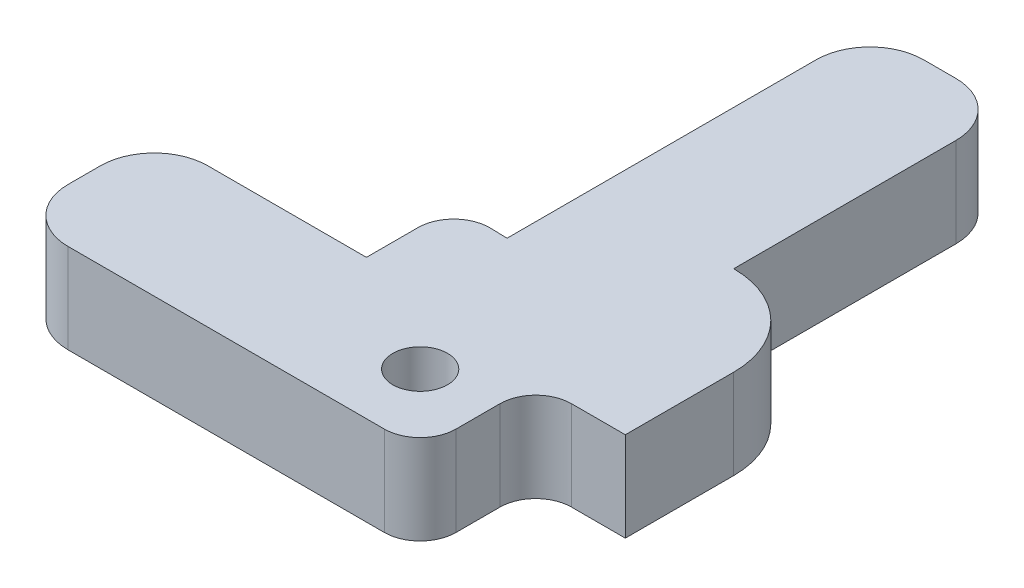
SolidWorks part; units mm, degrees
ref_plane "前视基准面" through (0, 0, 0) normal (0, 0, 1) x (1, 0, 0)
ref_plane "上视基准面" through (0, 0, 0) normal (0, 1, 0) x (1, 0, 0)
ref_plane "右视基准面" through (0, 0, 0) normal (1, 0, 0) x (0, 0, -1)
sketch "草图1" plane through (0, 0, 0) normal (0, 1, 0) x (1, 0, 0)
  line L0 (0, 0) -> (-3.75, 0) construction
  line L1 (8.75, 3.75) -> (8.75, 13.7657) construction
  line L2 (5.7467, -3.7343) -> (3.9, -3.7322) construction
  line L3 (-3.75, 8.75) -> (-3.75, 22) construction
  line L4 (-18.75, -0.75) -> (-18.75, 0.75) construction
  line L5 (5.7467, -3.7343) -> (5.7467, -6.2932) construction
  line L6 (0, 0) -> (3.75, 0) construction
  line L7 (3.75, 0) -> (8.75, 0) construction
  line L8 (8.75, 3.75) -> (8.75, -0.7343) construction
  line L9 (0.75, 29) -> (-0.75, 29) construction
  line L10 (-3.75, 0) -> (-8.75, 0) construction
  line L11 (5.7467, -3.7343) -> (5.7467, 16.2657) construction
  line L12 (-6.75, 3.75) -> (-10.75, 3.75) construction
  line L13 (5.7467, 16.2657) -> (5.75, 16.2657)
  line L14 (-8.75, -3.75) -> (-0.4105, -3.7275) construction
  line L15 (0, 0) -> (0, 32) construction
  line L16 (-10.75, -3.75) -> (-8.75, -3.75) construction
  line L17 (3.75, 22) -> (3.75, 16.7657) construction
  line L18 (-3.75, 22) -> (-3.75, 26) construction
  line L20 (-15.75, 3.75) -> (-10.75, 3.75) construction
  line L21 (3.75, 26) -> (3.75, 22) construction
  line L22 (-15.75, -3.75) -> (-10.75, -3.75) construction
  line L23 (3.75, 16.7657) -> (3.75, 13.7657) construction
  line L24 (5.7467, 13.7657) -> (5.75, 13.7657)
  line L25 (8.75, -3.75) -> (8.75, -0.7343) construction
  line L26 (5.75, -8.75) -> (-15.75, -8.75) construction
  line L27 (-18.75, -3.75) -> (-18.75, -0.75) construction
  line L28 (-15.75, -6.75) -> (5.75, -6.75) construction
  line L30 (-6.75, 3.75) -> (-6.75, 3.9)
  line L32 (0, 0) -> (-3.9, 0) construction
  line L33 (5.75, 13.7657) -> (5.7467, -3.7343) construction
  line L34 (3.9, -3.7322) -> (3.9, 2.55)
  line L35 (-0.9, 29) -> (0.9, 29)
  line L36 (3.9, 26) -> (3.9, 13.7657)
  line L37 (0, 0) -> (0, 3.9) construction
  line L38 (3.9, -3.9) -> (8.9, -3.9) construction
  line L39 (-18.75, 0.9) -> (-18.75, -0.9)
  line L40 (-15.75, -3.9) -> (0, -3.9)
  line L41 (0, -3.9) -> (3.9, -3.9)
  line L42 (3.9, -3.9) -> (3.9, -3.7322)
  line L43 (-6.9, 3.9) -> (-15.75, 3.9)
  line L44 (-3.9, 8.75) -> (-3.9, 26)
  line L45 (8.9, -3.9) -> (8.9, 2.55) construction
  line L46 (8.9, 2.55) -> (5.7479, 2.55)
  line L47 (8.9, 2.55) -> (8.9, 13.6)
  line L48 (3.9, 13.6) -> (3.9, 13.7657)
  line L49 (5.7479, 2.55) -> (3.9, 2.55)
  line L50 (3.9, 2.55) -> (3.9, -3.7322)
  line L51 (8.9, 2.55) -> (8.9, 13.6)
  line L52 (8.9, 13.6) -> (3.9, 13.6)
  line L54 (-3.9, 8.75) -> (-4.8512, 8.7732)
  line L55 (-6.9, 6.7738) -> (-6.9, 3.9)
  circle A0 centre (0, 0) radius 1.525
  arc A4 (-18.75, -0.75) -> (-15.75, -3.75) centre (-15.75, -0.75) ccw construction
  arc A5 (8.75, -0.7343) -> (5.7467, -3.7343) centre (5.75, -0.7343) cw construction
  arc A6 (-18.75, 0.75) -> (-15.75, 3.75) centre (-15.75, 0.75) cw construction
  arc A7 (-3.75, 26) -> (-0.75, 29) centre (-0.75, 26) cw construction
  arc A8 (3.75, 26) -> (0.75, 29) centre (0.75, 26) ccw construction
  arc A9 (-15.75, -8.75) -> (-18.75, -5.75) centre (-15.75, -5.75) cw construction
  arc A10 (5.75, -6.75) -> (8.75, -3.75) centre (5.75, -3.75) ccw construction
  arc A11 (-15.75, -6.75) -> (-18.75, -3.75) centre (-15.75, -3.75) cw construction
  arc A13 (-18.75, -0.9) -> (-15.75, -3.9) centre (-15.75, -0.9) ccw
  arc A14 (-15.75, 3.9) -> (-18.75, 0.9) centre (-15.75, 0.9) ccw
  arc A15 (0.9, 29) -> (3.9, 26) centre (0.9, 26) cw
  arc A16 (-3.9, 26) -> (-0.9, 29) centre (-0.9, 26) cw
  arc A17 (-4.8512, 8.7732) -> (-6.9, 6.7738) centre (-4.9, 6.7738) ccw
  dimension "D1" = 32
  dimension "D4" = 3
  dimension "D5" = 3
  dimension "D6" = 3
  dimension "D7" = 3
  dimension "D8" = 3
  dimension "D9" = 3
  dimension "D10" = 2
  dimension "D11" = 3
  dimension "D2" = 3.75
  dimension "D3" = 5
extrude "凸台-拉伸1" add sketch "草图1" along normal blind 5 contours L3 L2 A0 region at (-2.2553, 0, -8.5425)
sketch "草图4" plane through (0, 0, 0) normal (0, 1, 0) x (1, 0, 0)
  line L0 (-6.75, 3.75) -> (-3.75, 3.75) construction
  line L1 (-3.75, 3.75) -> (-3.75, 8.75) construction
  line L2 (-6.9, 3.9) -> (-3.9, 3.9)
  line L3 (-3.9, 3.9) -> (-3.9, 8.75)
  line L12 (-3.9, 8.75) -> (-4.8512, 8.7732)
  line L14 (3.9, -3.9) -> (3.9, 2.55)
  line L19 (-15.75, -3.9) -> (3.9, -3.9)
  line L20 (3.9, 13.6) -> (3.9, 26)
  line L21 (-18.75, 0.9) -> (-18.75, -0.9)
  line L22 (8.9, 2.55) -> (8.9, 13.6)
  line L36 (-3.9, 8.75) -> (-4.8512, 8.7732)
  line L40 (0.9, 29) -> (-0.9, 29)
  line L42 (-6.9, 6.7738) -> (-6.9, 3.9)
  line L43 (3.9, 2.55) -> (8.9, 2.55)
  line L44 (-6.9, 6.7738) -> (-6.9, 3.9)
  line L45 (8.9, 13.6) -> (3.9, 13.6)
  line L47 (-3.9, 26) -> (-3.9, 8.75)
  line L49 (-6.9, 3.9) -> (-15.75, 3.9)
  arc A5 (-4.8512, 8.7732) -> (-6.9, 6.7738) centre (-4.9, 6.7738) ccw
  arc A7 (-0.9, 29) -> (-3.9, 26) centre (-0.9, 26) ccw
  arc A8 (-4.8512, 8.7732) -> (-6.9, 6.7738) centre (-4.9, 6.7738) ccw
  arc A9 (3.9, 26) -> (0.9, 29) centre (0.9, 26) ccw
  arc A13 (-18.75, -0.9) -> (-15.75, -3.9) centre (-15.75, -0.9) ccw
  arc A15 (-15.75, 3.9) -> (-18.75, 0.9) centre (-15.75, 0.9) ccw
  dimension "D1" = 0
extrude "凸台-拉伸4" add sketch "草图4" against normal blind 4
fillet "圆角1" radius 2 1 edges at (3.9, 2.5, 3.9)
fillet "圆角2" radius 5 1 edges at (8.9, 2.5, -13.6)
fillet "圆角3" radius 2 1 edges at (3.9, 2.5, -2.55)
